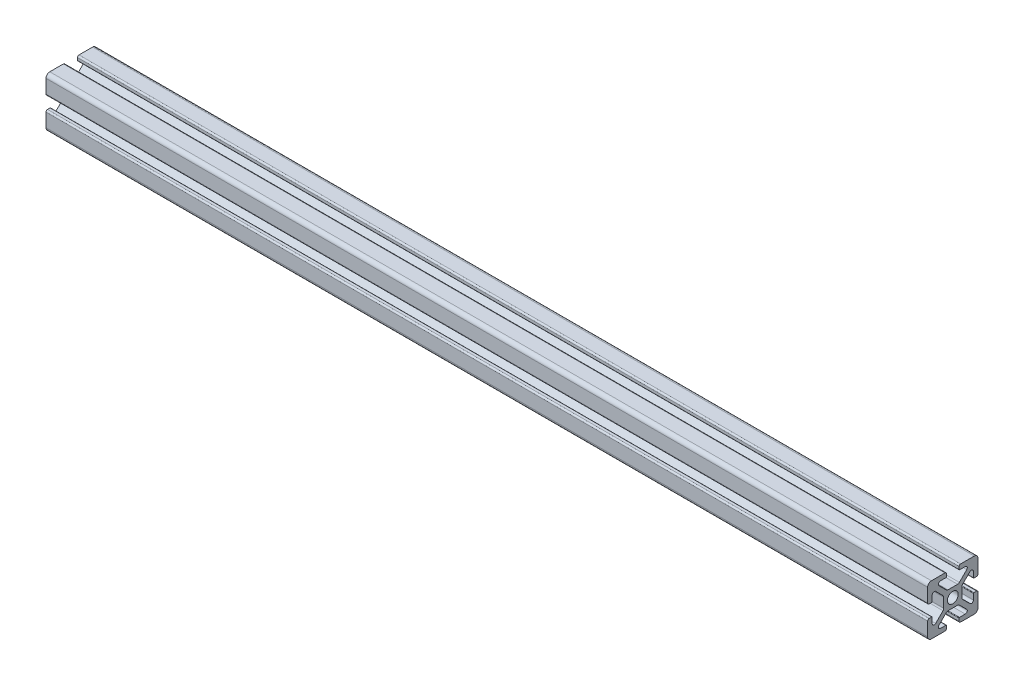
SolidWorks part; units mm, degrees
ref_plane "Front Plane" through (0, 0, 0) normal (0, 0, 1) x (1, 0, 0)
ref_plane "Top Plane" through (0, 0, 0) normal (0, 1, 0) x (1, 0, 0)
ref_plane "Right Plane" through (0, 0, 0) normal (1, 0, 0) x (0, 0, -1)
sketch "Sketch1" plane through (0, 0, 0) normal (1, 0, 0) x (0, 0, -1)
  line L0 (0, -10) -> (0, 10) construction
  line L1 (10, -10) -> (-10, -10)
  line L2 (10, -10) -> (10, 10)
  line L3 (10, 10) -> (0, 10)
  line L4 (-10, -10) -> (-10, 10)
  line L5 (10, -10) -> (-10, 10) construction
  line L6 (10, 10) -> (-10, -10) construction
  line L7 (10, 0) -> (-10, 0) construction
  line L8 (-2.5, 9.4) -> (-2.5, 8.3731)
  line L9 (-2.7, 8.1731) -> (-4.95, 8.1731)
  line L10 (-5.5157, 6.8075) -> (-2.6011, 3.8929)
  line L11 (-1.894, 3.6) -> (0, 3.6)
  line L12 (-5.3502, 4.0584) -> (-4.0584, 5.3502) construction
  line L13 (-3.825, 8.1731) -> (-3.825, 10) construction
  line L14 (-3.1, 10) -> (-10, 10)
  line L15 (-5.75, 7.3731) -> (5.75, 7.3731) construction
  circle A0 centre (0, 0) radius 2.15
  arc A1 (-4.95, 8.1731) -> (-5.5157, 6.8075) centre (-4.95, 7.3731) ccw
  arc A2 (-2.6011, 3.8929) -> (-1.894, 3.6) centre (-1.894, 4.6) ccw
  arc A3 (-2.5, 8.3731) -> (-2.7, 8.1731) centre (-2.7, 8.3731) cw
  arc A4 (-2.5, 9.4) -> (-3.1, 10) centre (-3.1, 9.4) ccw
  point P0 (0, 0)
  point P9 (0, 0)
  point P12 (0, 0)
  point P22 (-4.7043, 4.7043)
  point P32 (-2.5, 10)
  point P33 (-2.5, 8.8866)
  point P35 (-4.0584, 5.3502)
  point P37 (0, 7.3731)
  dimension "Center Hole Diameter" = 4.3
  dimension "D4" = 1
  dimension "D5" = 0.2
  dimension "D6" = 0.6
  dimension "D3" = 0.8
  dimension "Rail Height" = 20
  dimension "D7" = 6.4
  dimension "T Slot Width" = 5
  dimension "D10" = 10
  dimension "Rail Width" = 20
  dimension "D2" = 11.5
sketch "Sketch2" plane through (0, 0, 0) normal (0, 0, 1) x (1, 0, 0)
  line L0 (-132.4, 10) -> (-132.4, -10) construction
  line L1 (152.4, -10) -> (-152.4, -10) construction
  line L2 (152.4, -10) -> (152.4, 10) construction
  line L3 (152.4, 10) -> (-152.4, 10) construction
  line L4 (-152.4, -10) -> (-152.4, 10) construction
  line L5 (152.4, -10) -> (-152.4, 10) construction
  line L6 (152.4, 10) -> (-152.4, -10) construction
  line L7 (132.4, 10) -> (132.4, -10) construction
  point P0 (0, 0)
  point P12 (132.4, 0)
  dimension "Length" = 304.8
  dimension "D1" = 20
  dimension "D2" = 20
sketch "Sketch3" plane through (0, 0, 0) normal (1, 0, 0) x (0, 0, -1)
  line L0 (-5.5157, 6.8075) -> (-2.6011, 3.8929) construction
  line L5 (-3.1, 10) -> (-10, 10) construction
  line L6 (-2.5, 9.4) -> (-2.5, 8.3731) construction
  line L7 (-2.7, 8.1731) -> (-4.95, 8.1731) construction
  line L8 (-1.894, 3.6) -> (0, 3.6) construction
  line L9 (-5.5157, 6.8075) -> (-2.6011, 3.8929)
  line L10 (-10, 10) -> (0, 0) construction
  line L12 (-3.6, 1.894) -> (-3.6, 0)
  line L13 (-8.1731, 2.7) -> (-8.1731, 4.95)
  line L14 (-3.1, 10) -> (-8.5, 10)
  line L15 (-2.5, 9.4) -> (-2.5, 8.3731)
  line L16 (-2.7, 8.1731) -> (-4.95, 8.1731)
  line L17 (-1.894, 3.6) -> (0, 3.6)
  line L18 (-9.4, 2.5) -> (-8.3731, 2.5)
  line L19 (-10, 3.1) -> (-10, 8.5)
  line L20 (-6.8075, 5.5157) -> (-3.8929, 2.6011)
  line L21 (-3.6, 0) -> (-2.15, 0)
  line L22 (0, 3.6) -> (0, 2.15)
  arc A0 (-2.5, 9.4) -> (-3.1, 10) centre (-3.1, 9.4) ccw construction
  arc A1 (-2.7, 8.1731) -> (-2.5, 8.3731) centre (-2.7, 8.3731) ccw construction
  arc A2 (-4.95, 8.1731) -> (-5.5157, 6.8075) centre (-4.95, 7.3731) ccw construction
  arc A3 (-2.6011, 3.8929) -> (-1.894, 3.6) centre (-1.894, 4.6) ccw construction
  arc A4 (-2.5, 9.4) -> (-3.1, 10) centre (-3.1, 9.4) ccw
  arc A5 (-2.7, 8.1731) -> (-2.5, 8.3731) centre (-2.7, 8.3731) ccw
  arc A6 (-4.95, 8.1731) -> (-5.5157, 6.8075) centre (-4.95, 7.3731) ccw
  arc A7 (-2.6011, 3.8929) -> (-1.894, 3.6) centre (-1.894, 4.6) ccw
  arc A8 (-3.8929, 2.6011) -> (-3.6, 1.894) centre (-4.6, 1.894) cw
  arc A9 (-8.1731, 4.95) -> (-6.8075, 5.5157) centre (-7.3731, 4.95) cw
  arc A10 (-8.1731, 2.7) -> (-8.3731, 2.5) centre (-8.3731, 2.7) cw
  arc A11 (-9.4, 2.5) -> (-10, 3.1) centre (-9.4, 3.1) cw
  circle A12 centre (0, 0) radius 2.15 construction
  arc A13 (0, 2.15) -> (-2.15, 0) centre (0, 0) ccw
  arc A14 (-10, 8.5) -> (-8.5, 10) centre (-8.5, 8.5) cw
  dimension "D1" = 1.5
extrude "Boss-Extrude1" add sketch "Sketch3" against normal blind 175 and the other way blind 175
mirror "Mirror1" about plane through (0, 0, 0) normal (0, 1, 0) of bodies 104
mirror "Mirror2" about plane through (0, 0, 0) normal (0, 0, 1) of bodies 105
equation "\"D10@Sketch1\" = \"Rail Height@Sketch1\" / 2"
equation "\"D2@Sketch2\"=\"D1@Sketch2\""
